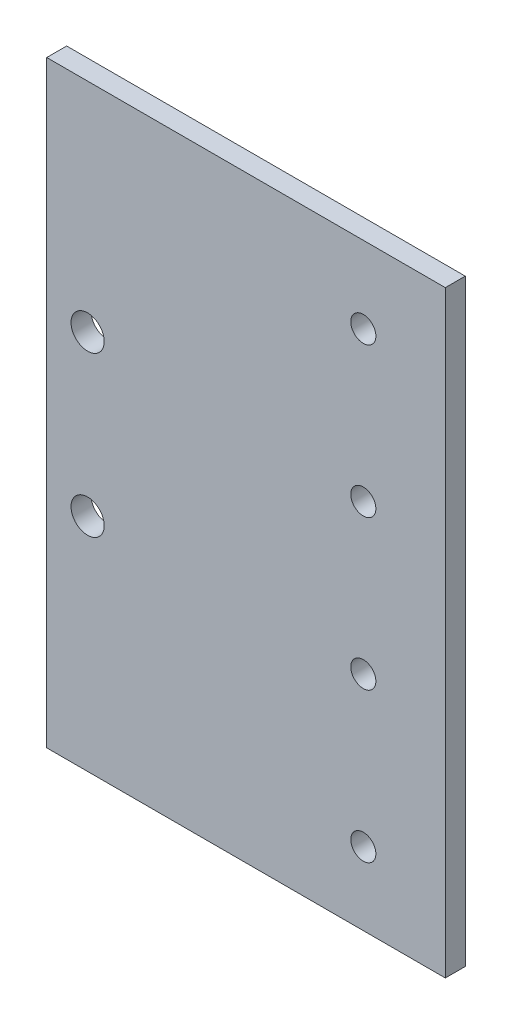
SolidWorks part; units mm, degrees
ref_plane "Front Plane" through (0, 0, 0) normal (0, 0, 1) x (1, 0, 0)
ref_plane "Top Plane" through (0, 0, 0) normal (0, 1, 0) x (1, 0, 0)
ref_plane "Right Plane" through (0, 0, 0) normal (1, 0, 0) x (0, 0, -1)
sketch "Sketch2" plane through (0, 0, 0) normal (0, 0, 1) x (1, 0, 0)
  line L0 (-123.0109, -74.4947) -> (-143.5848, -74.4947) construction
  line L1 (-123.0109, 0.5053) -> (-223.0109, 0.5053)
  line L2 (-123.0109, 0.5053) -> (-123.0109, -149.4947)
  line L3 (-123.0109, -149.4947) -> (-223.0109, -149.4947)
  line L4 (-223.0109, 0.5053) -> (-223.0109, -149.4947)
  line L5 (-143.5848, -74.4947) -> (-143.5848, -56.25) construction
  line L7 (-212.756, -54.0129) -> (-223.0109, -54.0129) construction
  line L8 (-212.756, -94.0129) -> (-223.0109, -94.0129) construction
  line L10 (-143.5848, -56.25) -> (-143.5848, -18.75) construction
  line L11 (-143.5848, -74.4947) -> (-143.5848, -93.75) construction
  line L12 (-143.5848, -93.75) -> (-143.5848, -131.25) construction
  circle A3 centre (-212.756, -54.0129) radius 4.165
  circle A4 centre (-212.756, -94.0129) radius 4.165
  circle A5 centre (-143.5848, -18.75) radius 3.15
  circle A6 centre (-143.5848, -56.25) radius 3.15
  circle A7 centre (-143.5848, -93.75) radius 3.15
  circle A8 centre (-143.5848, -131.25) radius 3.15
  dimension "D1" = 100
  dimension "D2" = 150
extrude "Boss-Extrude1" add sketch "Sketch2" along normal blind 5 contours L4 L3 L2 L1
sketch "Sketch3" plane through (0, 0, 0) normal (0, 0, -1) x (-1, 0, 0)
  circle A3 centre (212.756, -54.0129) radius 4.165
  circle A4 centre (212.756, -94.0129) radius 4.165
  circle A5 centre (143.5848, -18.75) radius 3.15
  circle A6 centre (143.5848, -56.25) radius 3.15
  circle A7 centre (143.5848, -93.75) radius 3.15
  circle A8 centre (143.5848, -131.25) radius 3.15
extrude "Cut-Extrude1" cut sketch "Sketch3" against normal blind 5
